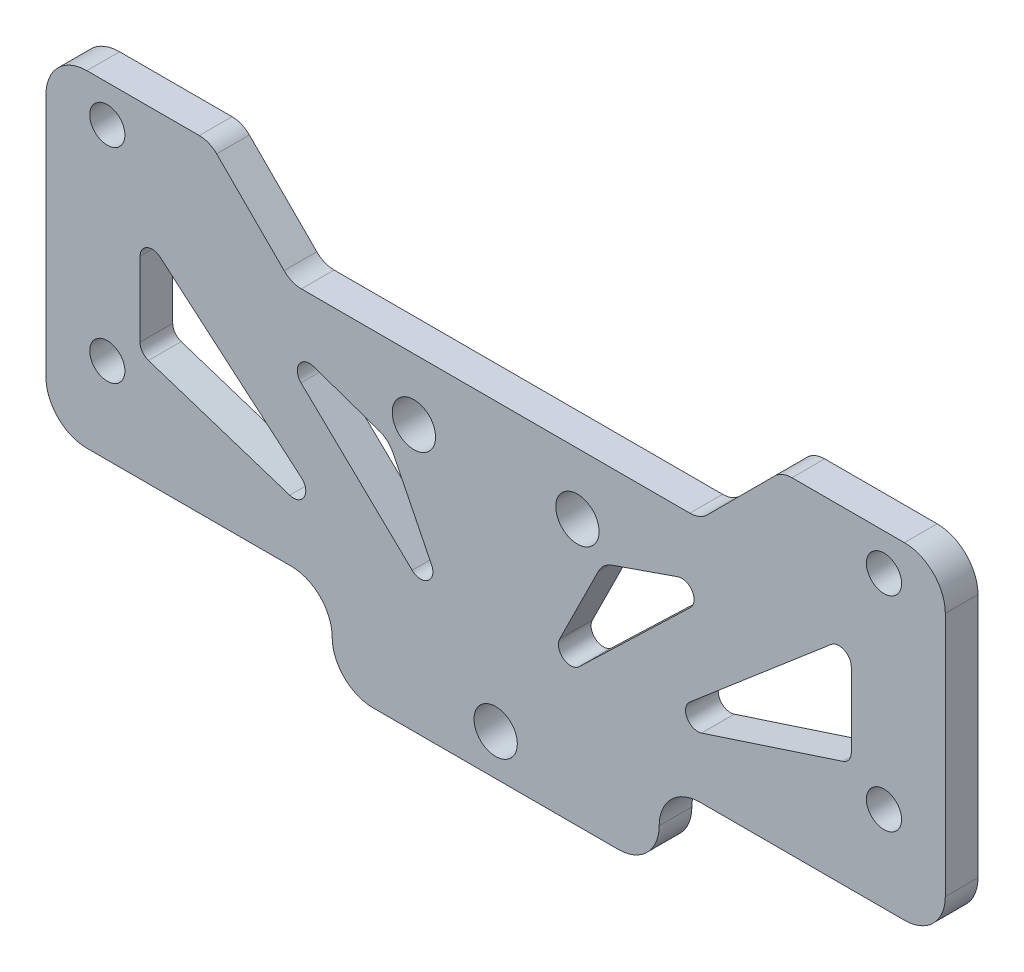
SolidWorks part; units mm, degrees
material "A-玻璃纤维"
ref_plane "前视基准面" through (0, 0, 0) normal (0, 0, 1) x (1, 0, 0)
ref_plane "上视基准面" through (0, 0, 0) normal (0, 1, 0) x (1, 0, 0)
ref_plane "右视基准面" through (0, 0, 0) normal (1, 0, 0) x (0, 0, -1)
sketch "草图1" plane through (0, 0, 0) normal (0, 0, 1) x (1, 0, 0)
  line L0 (0, 0) -> (20, 0) construction
  line L1 (-45, 17.5) -> (65, 17.5)
  line L2 (65, 17.5) -> (65, -22.5)
  line L3 (65, -22.5) -> (30, -22.5)
  line L4 (-45, -22.5) -> (-45, 17.5)
  line L5 (10, 0) -> (10, 39.8174) construction
  line L6 (57.5, 13) -> (57.5, -12) construction
  line L7 (-10, -22.5) -> (-10, -32.5)
  line L8 (-10, -32.5) -> (30, -32.5)
  line L9 (30, -32.5) -> (30, -22.5)
  line L10 (-10, -27.5) -> (30, -27.5) construction
  line L11 (-10, -22.5) -> (-45, -22.5)
  circle A0 centre (20, 0) radius 2.65
  circle A1 centre (0, 0) radius 2.65
  circle A2 centre (57.5, 13) radius 2.15
  circle A3 centre (57.5, -12) radius 2.15
  circle A4 centre (-37.5, -12) radius 2.15
  circle A5 centre (-37.5, 13) radius 2.15
  circle A6 centre (10, -27.5) radius 2.65
  dimension "D1" = 5.3
  dimension "D2" = 20
  dimension "D5" = 4.3
  dimension "D6" = 25
  dimension "D7" = 95
  dimension "D8" = 13
  dimension "D3" = 110
  dimension "D4" = 17.5
  dimension "D9" = 22.5
  dimension "D10" = 40
  dimension "D11" = 10
extrude "凸台-拉伸1" add sketch "草图1" along normal blind 4
fillet "圆角1" radius 5 8 edges at (30, -22.5, 2) (-45, 17.5, 2) (-45, -22.5, 2) (65, 17.5, 2) (65, -22.5, 2) (30, -32.5, 2) (-10, -32.5, 2) (-10, -22.5, 2)
sketch "草图3" plane through (0, 0, 4) normal (0, 0, 1) x (1, 0, 0)
  line L0 (10, -27.5) -> (10, 27.8196) construction
  line L1 (-25, 17.5) -> (-15, 7.5)
  line L2 (60, 17.5) -> (-40, 17.5) construction
  line L3 (-15, 7.5) -> (35, 7.5)
  line L4 (35, 7.5) -> (45, 17.5)
  line L5 (45, 17.5) -> (-25, 17.5)
  dimension "D1" = 70
  dimension "D2" = 10
  dimension "D3" = 45
extrude "切除-拉伸1" cut sketch "草图3" against normal through all
fillet "圆角2" radius 3 4 edges at (45, 17.5, 2) (35, 7.5, 2) (-25, 17.5, 2) (-15, 7.5, 2)
sketch "草图4" plane through (0, 0, 4) normal (0, 0, 1) x (1, 0, 0)
  line L0 (-37.5, 13) -> (-37.5, -12) construction
  line L1 (-37.5, -12) -> (10, -27.5) construction
  line L2 (10, -27.5) -> (57.5, -12) construction
  line L3 (57.5, -12) -> (57.5, 13) construction
  line L4 (57.5, 13) -> (20, 0) construction
  line L11 (20, 0) -> (0, 0) construction
  line L14 (0, 0) -> (-37.5, 13) construction
  line L15 (0, 0) -> (10, -27.5) construction
  line L16 (10, -27.5) -> (20, 0) construction
  line L17 (57.5, 13) -> (10, -27.5) construction
  line L19 (10, -27.5) -> (10, 0) construction
  line L21 (38.7435, 2.2642) -> (23.1087, -3.1559)
  line L24 (27.9819, -17.4246) -> (53.5, -9.0977)
  line L25 (53.5, -9.0977) -> (53.5, 4.3329)
  line L26 (53.5, 4.3329) -> (27.9819, -17.4246)
  line L27 (10, -15.7953) -> (14.2892, -4) construction
  line L28 (14.2892, -4) -> (5.7108, -4) construction
  line L29 (5.7108, -4) -> (10, -15.7953) construction
  line L30 (-33.5, -9.0977) -> (-33.5, 4.3329)
  line L31 (-7.9819, -17.4246) -> (-33.5, -9.0977)
  line L32 (-33.5, 4.3329) -> (-7.9819, -17.4246)
  line L33 (-18.7435, 2.2642) -> (-3.1087, -3.1559)
  line L36 (38.7435, 2.2642) -> (18.9394, -14.6214) construction
  line L37 (18.9394, -14.6214) -> (23.1087, -3.1559) construction
  line L38 (23.1087, -3.1559) -> (14, -21.5)
  line L39 (14, -21.5) -> (38.7435, 2.2642)
  line L41 (-3.1087, -3.1559) -> (6, -21.5)
  line L42 (6, -21.5) -> (-18.7435, 2.2642)
  dimension "D1" = 4
  dimension "D4" = 4
  dimension "D2" = 4
  dimension "D3" = 4
  dimension "D5" = 6
extrude "切除-拉伸2" cut sketch "草图4" against normal through all and the other way through all
fillet "圆角4" radius 1.5 10 edges at (53.5, 4.3329, 2) (53.5, -9.0977, 2) (-33.5, -9.0977, 2) (-33.5, 4.3329, 2) (38.7435, 2.2642, 2) (14, -21.5, 2) (-18.7435, 2.2642, 2) (6, -21.5, 2)
fillet "圆角6" radius 3 2 edges at (23.1087, -3.1559, 2) (-3.1087, -3.1559, 2)
